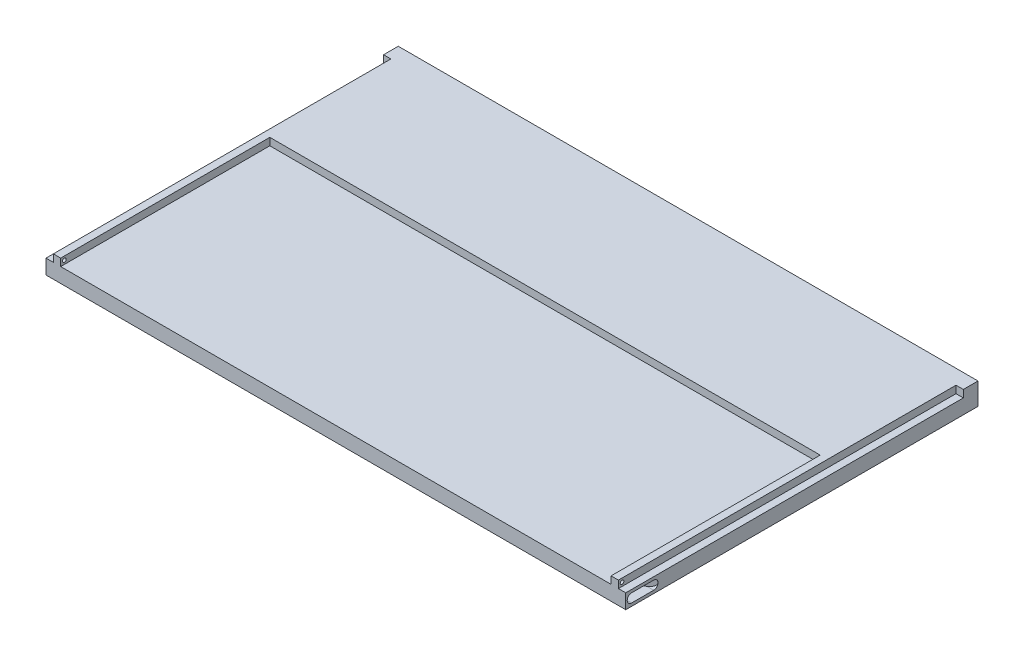
SolidWorks part; units mm, degrees
other "Markup1"
sketch "Sketch12" plane through (250.825, 22.225, 158.75) normal (0.1153, 0.0728, 0.9907) x (0.9687, -0.2289, -0.0959)
material "6061 Alloy"
ref_plane "Front Plane" through (0, 0, 0) normal (0, 0, 1) x (1, 0, 0)
ref_plane "Top Plane" through (0, 0, 0) normal (0, 1, 0) x (1, 0, 0)
ref_plane "Right Plane" through (0, 0, 0) normal (1, 0, 0) x (0, 0, -1)
sketch "Sketch1" plane through (0, 0, 0) normal (0, 1, 0) x (1, 0, 0)
  line L1 (-244.475, 152.4) -> (244.475, 152.4)
  line L2 (-244.475, 152.4) -> (-244.475, -152.4)
  line L3 (-244.475, -152.4) -> (244.475, -152.4)
  line L4 (244.475, 152.4) -> (244.475, -152.4)
  line L5 (-244.475, 152.4) -> (244.475, -152.4) construction
  line L6 (-244.475, -152.4) -> (244.475, 152.4) construction
  point P0 (0, 0)
  dimension "D1" = 488.95
  dimension "D2" = 304.8
extrude "Boss-Extrude1" add sketch "Sketch1" along normal blind 12.7
sketch "Sketch2" plane through (0, 12.7, 0) normal (0, 1, 0) x (1, 0, 0)
  line L0 (-244.475, -152.4) -> (244.475, -152.4) construction
  line L1 (-244.475, 152.4) -> (-238.125, 152.4)
  line L2 (-244.475, 152.4) -> (-244.475, -152.4)
  line L3 (-244.475, -152.4) -> (-238.125, -152.4)
  line L4 (-238.125, 28.575) -> (-238.125, -152.4)
  line L5 (244.475, 152.4) -> (-244.475, 152.4) construction
  line L6 (244.475, 152.4) -> (238.125, 152.4)
  line L7 (244.475, 152.4) -> (244.475, -152.4)
  line L8 (244.475, -152.4) -> (238.125, -152.4)
  line L9 (238.125, 28.575) -> (238.125, -152.4)
  line L10 (-238.125, 152.4) -> (238.125, 152.4)
  line L12 (-238.125, 28.575) -> (238.125, 28.575)
  point P14 (-241.3, -152.4)
  dimension "D1" = 6.35
  dimension "D2" = 180.975
extrude "Boss-Extrude2" add sketch "Sketch2" along normal blind 6.35
sketch "Sketch3" plane through (-244.475, 0, 0) normal (-1, 0, 0) x (0, 0, 1)
  line L0 (152.4, 19.05) -> (152.4, 0) construction
  line L1 (-152.4, 19.05) -> (152.4, 19.05) construction
  circle A0 centre (149.225, 15.875) radius 1.5875
  dimension "D3" = 3.175
  dimension "D1" = 3.175
  dimension "D2" = 3.175
extrude "Cut-Extrude1" cut sketch "Sketch3" against normal through all
sketch "Sketch4" plane through (0, 0, 152.4) normal (0, 0, 1) x (1, 0, 0)
  line L0 (-244.475, 19.05) -> (-244.475, 0) construction
  line L1 (-244.475, 12.7) -> (-250.825, 12.7)
  line L2 (-244.475, 12.7) -> (-244.475, 0)
  line L3 (-244.475, 0) -> (-250.825, 0)
  line L4 (-250.825, 12.7) -> (-250.825, 0)
  line L5 (-244.475, 0) -> (244.475, 0) construction
  dimension "D1" = 12.7
  dimension "D2" = 6.35
extrude "Boss-Extrude3" add sketch "Sketch4" against normal blind 292.1
sketch "Sketch5" plane through (-244.475, 0, 0) normal (-1, 0, 0) x (0, 0, 1)
  line L0 (-152.4, 0) -> (-139.7, 0) construction
  line L1 (-152.4, 19.05) -> (-139.7, 19.05)
  line L2 (-152.4, 19.05) -> (-152.4, 0)
  line L3 (-152.4, 0) -> (-139.7, 0)
  line L4 (-139.7, 19.05) -> (-139.7, 0)
  line L5 (-139.7, 0) -> (-139.7, 12.7) construction
extrude "Boss-Extrude4" add sketch "Sketch5" along normal up to surface (6.35 mm away) up to face at (-250.825, 6.35, 6.35)
mirror "Mirror1" about plane through (0, 0, 0) normal (1, 0, 0) of "Boss-Extrude4", "Boss-Extrude3"
sketch "Sketch6" plane through (-244.475, 0, 0) normal (-1, 0, 0) x (0, 0, 1)
  line L0 (147.32, 6.35) -> (128.27, 6.35) construction
  line L1 (147.32, 2.54) -> (128.27, 2.54)
  line L2 (147.32, 10.16) -> (128.27, 10.16)
  line L3 (152.4, 19.05) -> (152.4, 12.7) construction
  line L5 (152.4, 12.7) -> (152.4, 0) construction
  arc A0 (147.32, 2.54) -> (147.32, 10.16) centre (147.32, 6.35) ccw
  arc A1 (128.27, 10.16) -> (128.27, 2.54) centre (128.27, 6.35) ccw
  point P2 (137.795, 6.35)
  point P11 (152.4, 6.35)
  dimension "D1" = 19.05
  dimension "D2" = 5.08
  dimension "D3" = 7.62
extrude "Cut-Extrude2" cut sketch "Sketch6" against normal blind 25.4 from surface starting at face at (-250.825, 10.5833, -46.5667)
extrude "Cut-Extrude3" cut sketch "Sketch6<2>" along normal blind 25.4 from surface starting at face at (250.825, 10.5833, -46.5667)
sketch "Sketch6<2>" plane through (-244.475, 0, 0) normal (-1, 0, 0) x (0, 0, 1) same geometry as "Sketch6"
sketch "Sketch11" plane through (0, 0, 0) normal (0, -1, 0) x (1, 0, 0)
  line L0 (-250.825, 124.46) -> (-225.425, 124.46)
  line L1 (-225.425, 124.46) -> (-225.425, 140.97)
  line L2 (-225.425, 140.97) -> (-250.825, 124.46)
  line L3 (-225.425, 128.27) -> (-225.425, 147.32) construction
  dimension "D1" = 10.16
extrude "Boss-Extrude5" add sketch "Sketch11" against normal up to surface (10.16 mm away) from surface up to face at (-238.125, 10.16, 137.795) starting at face at (-238.125, 2.54, 137.795)
mirror "Mirror2" about plane through (0, 0, 0) normal (1, 0, 0) of "Boss-Extrude5"
